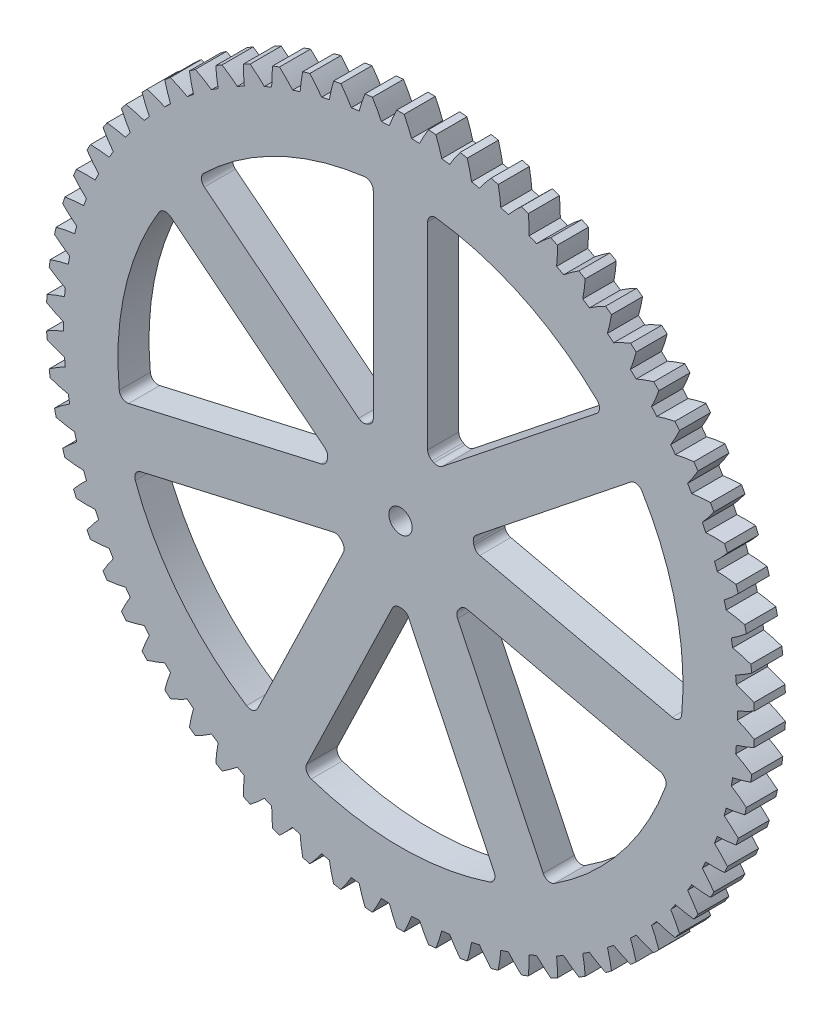
SolidWorks part; units mm, degrees
material "ABS"
ref_plane "Front Plane" through (0, 0, 0) normal (0, 0, 1) x (1, 0, 0)
ref_plane "Top Plane" through (0, 0, 0) normal (0, 1, 0) x (1, 0, 0)
ref_plane "Right Plane" through (0, 0, 0) normal (1, 0, 0) x (0, 0, -1)
sketch "Definition Drawing" plane through (0, 0, 0) normal (0, 0, 1) x (1, 0, 0)
  line L0 (45.5634, 0) -> (43.5634, 0) construction
  line L1 (0, 0) -> (-18.3231, 35.9926) construction
  line L2 (0, 0) -> (0, 45.5634) construction
  line L3 (0, 0) -> (2.0717, 40.335) construction
  line L4 (-18.3231, 35.9926) -> (0.4723, 45.5609) construction
  line L5 (0, 0) -> (0.9499, 44.5533) construction
  line L6 (0, 0) -> (0.9999, 44.5522) construction
  line L7 (0, 0) -> (-13.4816, 38.0716) construction
  line L8 (-13.4816, 38.0716) -> (1.4292, 43.3517) construction
  line L9 (0, 0) -> (-8.4108, 39.5027) construction
  line L10 (-8.4108, 39.5027) -> (1.9034, 41.6987) construction
  line L11 (0, 0) -> (-3.1967, 40.2614) construction
  line L12 (-3.1967, 40.2614) -> (2.0594, 40.6788) construction
  circle A0 centre (0, 0) radius 40.3881 construction
  circle A1 centre (0, 0) radius 43.5634 construction
  circle A2 centre (0, 0) radius 44.5634 construction
  circle A3 centre (0, 0) radius 45.5634 construction
  circle A4 centre (0, 0) radius 43.3634 construction
  arc A5 (0.9499, 44.5533) -> (0.9999, 44.5522) centre (0, 0) cw construction
  spline S0 degree 3 poles (2.0717, 40.335) (2.0725, 40.7943) (1.7852, 42.6159) (1.0915, 44.3343) (0.4723, 45.5609) knots 0 0 0 0 0.250014 1 1 1 1 construction
  point P13 (44.5634, 0)
  dimension "D4" = 89.1268
  dimension "D5" = 80.7763
  dimension "D1" = 2
  dimension "D2" = 0.2
  dimension "D3" = 1.286
  dimension "D6" = 0.05
  dimension "D7" = 29.92
  dimension "D11" = 15.8181
  dimension "D12" = 10.5454
  dimension "D13" = 5.2727
  dimension "D8" = 22.44
  dimension "D9" = 14.96
  dimension "D10" = 7.48
sketch "Sketch5" plane through (0, 0, 0) normal (0, 0, 1) x (1, 0, 0)
  circle A1 centre (0, 0) radius 43.3634
  circle A2 centre (0, 0) radius 1.5
  circle A3 centre (0, 0) radius 43.3634 construction
  dimension "D1" = 3
extrude "Extrude Body" add sketch "Sketch5" along normal mid plane 4
sketch "Sketch6" plane through (0, 0, 0) normal (0, 0, 1) x (1, 0, 0)
  line L0 (0, 45.5634) -> (0, 0) construction
  line L4 (2.0717, 40.335) -> (0.0769, 1.498)
  line L5 (0, 0) -> (2.0717, 40.335) construction
  line L6 (-2.0717, 40.335) -> (-0.0769, 1.498)
  arc A0 (0.4723, 45.5609) -> (-0.4723, 45.5609) centre (0, 0) ccw
  arc A3 (0.0769, 1.498) -> (-0.0769, 1.498) centre (0, 0) ccw
  circle A4 centre (0, 0) radius 1.5 construction
  spline S0 degree 3 poles (2.0717, 40.335) (2.0725, 40.7943) (1.7852, 42.6159) (1.0915, 44.3343) (0.4723, 45.5609) knots 0 0 0 0 0.250014 1 1 1 1
  spline S1 degree 3 poles (-2.0717, 40.335) (-2.0725, 40.7943) (-1.7852, 42.6159) (-1.0915, 44.3343) (-0.4723, 45.5609) knots 0 0 0 0 0.250014 1 1 1 1
extrude "Extrude Tooth" add sketch "Sketch6" along normal mid plane 4
pattern_circular "CirPattern1" count 70 over 360 about axis through (0, 0, 2) along (0, 0, -1) of "Extrude Tooth"
sketch "Sketch8" plane through (0, 0, 0) normal (0, 0, 1) x (1, 0, 0)
  line L6 (0, 45.5634) -> (0, 0) construction
  line L7 (0, 0) -> (35.6229, 28.4083) construction
  line L8 (3.5, 35.0759) -> (3.5, 9.671)
  line L9 (5.3789, 8.7662) -> (25.2412, 24.6059)
  circle A2 centre (0, 0) radius 45.5634 construction
  arc A20 (25.3139, 26.1056) -> (4.6273, 36.0678) centre (0, 0) ccw
  circle A21 centre (0, 0) radius 43.3634 construction
  arc A23 (25.2412, 24.6059) -> (25.3139, 26.1056) centre (24.6177, 25.3877) ccw
  arc A24 (5.3789, 8.7662) -> (4.3096, 8.6529) centre (4.7554, 9.548) cw
  arc A25 (3.5, 9.671) -> (4.0781, 8.7643) centre (4.5, 9.671) ccw
  arc A26 (3.5, 35.0759) -> (4.6273, 36.0678) centre (4.5, 35.0759) cw
  arc A27 (4.3096, 8.6529) -> (4.0781, 8.7643) centre (0, 0) ccw
  circle A28 centre (0, 0) radius 1.5 construction
  dimension "D6" = 1
  dimension "D4" = 7
  dimension "D5" = 7
  dimension "D2" = 8.1667
  dimension "D3" = 51.429
extrude "Cut Spoke" cut sketch "Sketch8" against normal through all and the other way through all
pattern_circular "Pattern Spokes" count 7 over 360 about axis through (0, 0, 0) along (0, 0, 1) of "Cut Spoke"
equation "\"nTeeth\"= 70"
equation "\"xThickness\" = 4"
equation "\"dShaft\"= 3"
equation "\"aPressure\"=25"
equation "\"pitch\"= 4"
equation "\"rHeight\"= 2"
equation "\"rClearance\"= 0.2"
equation "\"xClearance\"=0.05"
equation "\"rFillet\"= 1"
equation "\"nSpokes\"= int ( ( \"nTeeth\" - 1 ) / 10 ) + 1'rounds up"
equation "\"dPitch\"= \"nTeeth\" * \"pitch\" / pi"
equation "\"xWall\"= IIF ( \"nTeeth\" > 30 , \"nTeeth\" / 10 , 3 )"
equation "\"dBase\"= \"dPitch\" * cos ( \"aPressure\" )"
equation "\"rOuter\"= \"dPitch\" / 2 + \"rHeight\" / 2"
equation "\"xInvolute\"= sqr ( \"rOuter\" ^ 2 - ( \"dBase\" / 2 ) ^ 2 )"
equation "\"aInvolute\"= 360 * \"xInvolute\" / ( \"dBase\" / 2 ) / 2 / pi"
equation "\"D1@Definition Drawing\" = \"rHeight\""
equation "\"D2@Definition Drawing\" = \"rClearance\""
equation "\"D4@Definition Drawing\" = \"dPitch\""
equation "\"D6@Definition Drawing\" = \"xClearance\""
equation "\"D5@Definition Drawing\" = \"dBase\""
equation "\"D7@Definition Drawing\" = \"aInvolute\""
equation "\"D11@Definition Drawing\" = \"xInvolute\" * 0.75"
equation "\"D12@Definition Drawing\" = \"xInvolute\" * 0.5"
equation "\"D13@Definition Drawing\" = \"xInvolute\" * 0.25"
equation "\"D8@Definition Drawing\" = \"aInvolute\" * 0.75"
equation "\"D9@Definition Drawing\" = \"aInvolute\" * 0.5"
equation "\"D10@Definition Drawing\" = \"aInvolute\" * 0.25"
equation "\"D1@Extrude Body\"=\"xThickness\""
equation "\"D1@Sketch5\"=\"dShaft\""
equation "\"D3@Definition Drawing\" = 360 / \"nTeeth\" / 2 / 2"
equation "\"D5@Sketch8\"=\"xWall\""
equation "\"D1@Sketch8\"=\"xWall\""
equation "\"D4@Sketch8\"=\"xWall\""
equation "\"D6@Sketch8\"=\"rFillet\""
equation "\"D1@Pattern Spokes\" = \"nSpokes\""
equation "\"rHub\"= IIF ( \"xWall\" * \"nSpokes\" / 6 > \"xWall\" , \"xWall\" * \"nSpokes\" / 6 , \"xWall\" )"
equation "\"D2@Sketch8\"=\"rHub\""
equation "\"D3@Sketch8\"=360/\"nSpokes\""
equation "\"D1@Extrude Tooth\" = \"xThickness\""
equation "\"D1@CirPattern1\"=\"nTeeth\""
